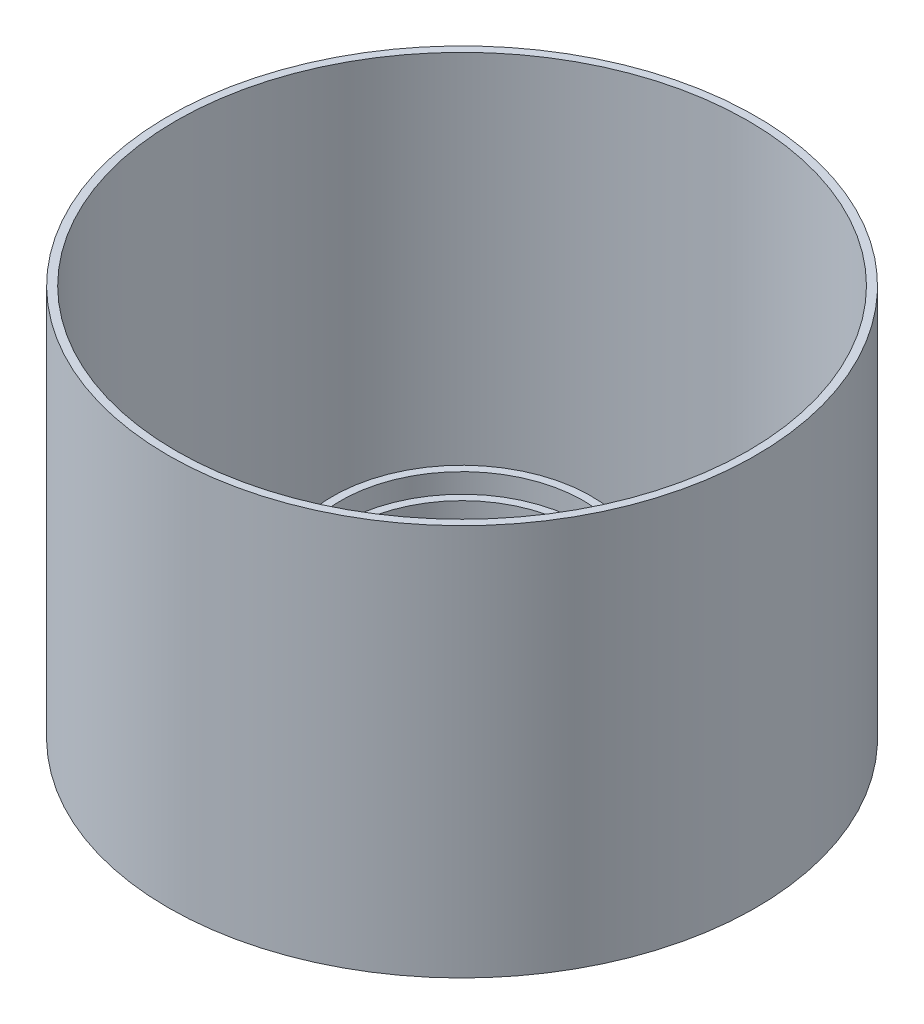
SolidWorks part; units mm, degrees
ref_plane "Front Plane" through (0, 0, 0) normal (0, 0, 1) x (1, 0, 0)
ref_plane "Top Plane" through (0, 0, 0) normal (0, 1, 0) x (1, 0, 0)
ref_plane "Right Plane" through (0, 0, 0) normal (1, 0, 0) x (0, 0, -1)
sketch "Sketch1" plane through (0, 0, 0) normal (0, 1, 0) x (1, 0, 0)
  circle A0 centre (0, 0) radius 75
  dimension "D1" = 150
extrude "Boss-Extrude1" add sketch "Sketch1" along normal blind 100
shell "Shell1" thickness 2 removed face at (0, 100, 75)
sketch "Sketch2" plane through (0, 2, 0) normal (0, 1, 0) x (1, 0, 0)
  circle A0 centre (0, 0) radius 29
  dimension "D1" = 58
extrude "Extrude-Thin1" add sketch "Sketch2" along normal blind 35 thin thin type one direction wall 4
sketch "Sketch3" plane through (0, 37, 0) normal (0, 1, 0) x (1, 0, 0)
  circle A0 centre (0, 0) radius 31
  dimension "D1" = 62
extrude "Cut-Extrude1" cut sketch "Sketch3" against normal blind 5
sketch "Sketch4" plane through (0, 2, 0) normal (0, 1, 0) x (1, 0, 0)
  circle A0 centre (0, 0) radius 29
extrude "Cut-Extrude2" cut sketch "Sketch4" against normal blind 2
